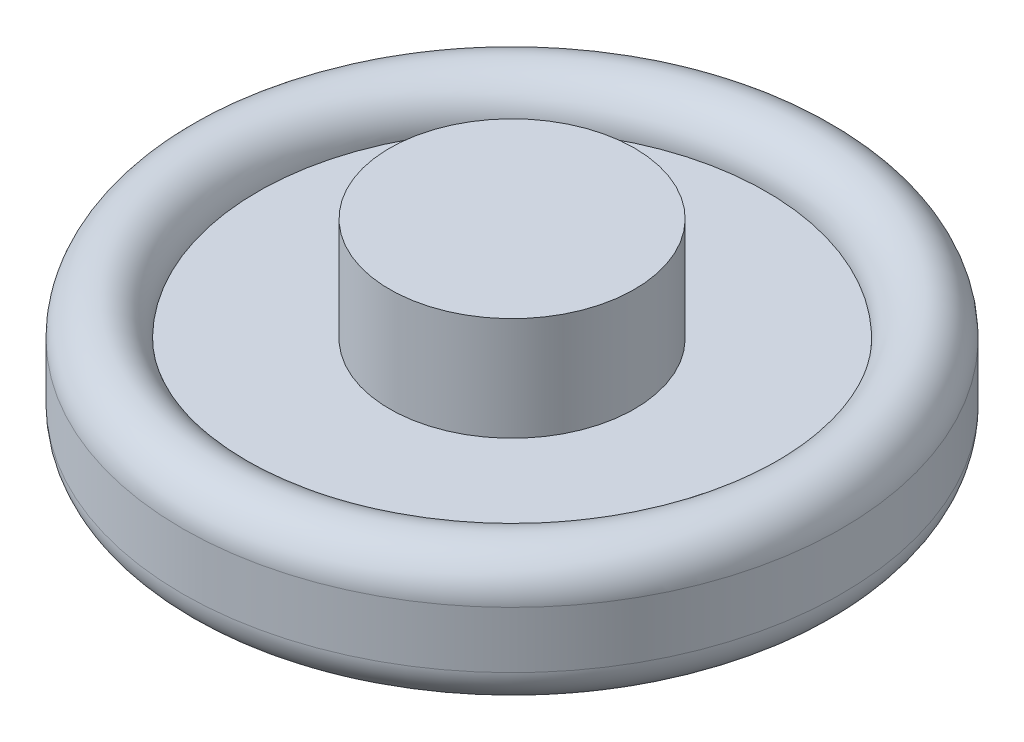
SolidWorks part; units mm, degrees
material "Резина"
ref_plane "Спереди" through (0, 0, 0) normal (0, 0, 1) x (1, 0, 0)
ref_plane "Сверху" through (0, 0, 0) normal (0, 1, 0) x (1, 0, 0)
ref_plane "Справа" through (0, 0, 0) normal (1, 0, 0) x (0, 0, -1)
sketch "Эскиз1" plane through (0, 0, 0) normal (0, 0, 1) x (1, 0, 0)
  line L0 (15.5, -1.5) -> (15.5, 1.5) construction
  line L1 (13.5, -1.5) -> (13.5, 1.5)
  line L2 (17.5, -1.5) -> (17.5, 1.5)
  line L3 (0, 0) -> (0, -10.6855) construction
  line L4 (0, -1.5) -> (13.5, -1.5)
  line L5 (0, -1.5) -> (0, 1.5)
  line L6 (0, 1.5) -> (13.5, 1.5)
  line L7 (13.5, -1.5) -> (13.5, 1.5)
  line L8 (0, -1.5) -> (13.5, 1.5) construction
  line L9 (0, 1.5) -> (13.5, -1.5) construction
  arc A0 (13.5, -1.5) -> (17.5, -1.5) centre (15.5, -1.5) ccw
  arc A1 (17.5, 1.5) -> (13.5, 1.5) centre (15.5, 1.5) ccw
  point P2 (15.5, 0)
  point P7 (6.75, 0)
  dimension "D2" = 2
  dimension "D1" = 15.5
  dimension "D3" = 3
  dimension "D4" = 3
revolve "Повернуть1" add sketch "Эскиз1" angle 360 about L3 region at (15.5, 0, 0)
sketch "Эскиз4" plane through (0, 0, 0) normal (0, 1, 0) x (1, 0, 0)
  circle A0 centre (0, 0) radius 6.5
  dimension "D1" = 13
extrude "Бобышка-Вытянуть1" add sketch "Эскиз4" along normal blind 7
ref_plane "Плоскость1" through (0, 4.75, 0) normal (0, -1, 0) x (-1, 0, 0)
sketch "Эскиз5" plane through (0, 4.75, 0) normal (0, -1, 0) x (-1, 0, 0)
  line L1 (2.3094, 4) -> (-2.3094, 4)
  line L2 (-2.3094, 4) -> (-4.6188, 0)
  line L3 (-4.6188, 0) -> (-2.3094, -4)
  line L4 (-2.3094, -4) -> (2.3094, -4)
  line L5 (2.3094, -4) -> (4.6188, 0)
  line L6 (4.6188, 0) -> (2.3094, 4)
  circle A0 centre (0, 0) radius 4 construction
  dimension "D1" = 8
extrude "Вырез-Вытянуть1" cut sketch "Эскиз5" along normal blind 1.5
extrude "Вырез-Вытянуть2" cut sketch "Эскиз5<2>" along normal blind 1.5 from offset 3.5
sketch "Эскиз5<2>" plane through (0, 4.75, 0) normal (0, -1, 0) x (-1, 0, 0) same geometry as "Эскиз5"
sketch "Эскиз6" plane through (0, -1.5, 0) normal (0, -1, 0) x (1, 0, 0)
  circle A0 centre (0, 0) radius 3
  dimension "D1" = 6
extrude "Вырез-Вытянуть3" cut sketch "Эскиз6" against normal up to surface (6.25 mm away) up to face at (0, 4.75, 0)
